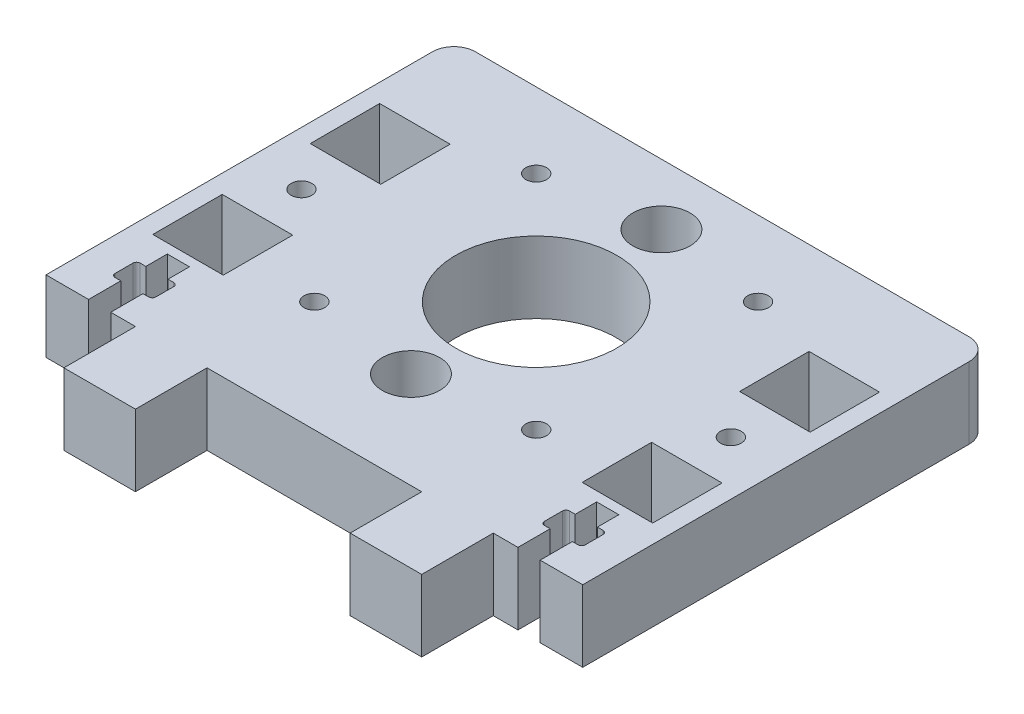
SolidWorks part; units mm, degrees
ref_plane "Front Plane" through (0, 0, 0) normal (0, 0, 1) x (1, 0, 0)
ref_plane "Top Plane" through (0, 0, 0) normal (0, 1, 0) x (1, 0, 0)
ref_plane "Right Plane" through (0, 0, 0) normal (1, 0, 0) x (0, 0, -1)
sketch "Sketch1" plane through (0, 0, 0) normal (0, 1, 0) x (1, 0, 0)
  line L0 (0, 31) -> (0, -8.5) construction
  line L1 (-34.5, 31) -> (0, 31)
  line L2 (-37.5, 28) -> (-37.5, -26)
  line L3 (-37.5, -26) -> (-25, -26)
  line L4 (0, 31) -> (0, 16.25)
  line L5 (0, -6.25) -> (0, -8.5)
  line L6 (0, -16.5) -> (0, -26) construction
  line L7 (-11.25, 5) -> (0, 5) construction
  line L8 (0, -16.5) -> (0, -26)
  line L9 (-30, 18.05) -> (-30, 8.35) construction
  line L10 (-37.5, 2.2) -> (0, 2.2) construction
  line L11 (-34.925, 18.05) -> (-25.075, 18.05)
  line L12 (-34.925, 18.05) -> (-34.925, 8.35)
  line L13 (-34.925, 8.35) -> (-25.075, 8.35)
  line L14 (-25.075, 18.05) -> (-25.075, 8.35)
  line L15 (-34.925, 18.05) -> (-25.075, 8.35) construction
  line L16 (-34.925, 8.35) -> (-25.075, 18.05) construction
  line L17 (-34.925, -3.95) -> (-25.075, -13.65) construction
  line L18 (-34.925, -13.65) -> (-25.075, -3.95) construction
  line L19 (-25.075, -13.65) -> (-25.075, -3.95)
  line L20 (-34.925, -3.95) -> (-25.075, -3.95)
  line L21 (-34.925, -13.65) -> (-34.925, -3.95)
  line L22 (-34.925, -13.65) -> (-25.075, -13.65)
  line L23 (-30, -3.95) -> (-30, -13.65) construction
  line L24 (-30, -8.8) -> (-30, 13.2) construction
  line L25 (0, 5) -> (-15.5, 20.5) construction
  line L35 (-15, -26) -> (0, -26)
  line L43 (-20, -36) -> (-20, -24.65) construction
  line L44 (-15, -26) -> (-15, -36)
  line L45 (-15, -36) -> (-25, -36)
  line L46 (-25, -36) -> (-25, -26)
  arc A1 (-34.5, 31) -> (-37.5, 28) centre (-34.5, 28) ccw
  arc A2 (0, 16.25) -> (0, -6.25) centre (0, 5) ccw
  circle A4 centre (-15.5, 20.5) radius 1.45
  circle A6 centre (-15.5, -10.5) radius 1.45
  circle A7 centre (-30, 2.2) radius 1.45
  arc A10 (0, -8.5) -> (0, -16.5) centre (0, -12.5) ccw
  point P0 (0, 0)
  point P28 (-30, 13.2)
  point P39 (-30, -8.8)
  dimension "D7" = 22.5
  dimension "D17" = 8
  dimension "D14" = 2.9
  dimension "D6" = 3
  dimension "D19" = 2.9
  dimension "D1" = 57
  dimension "D9" = 9.85
  dimension "D10" = 9.7
  dimension "D22" = 10
  dimension "D23" = 10
  dimension "D16" = 17.5
  dimension "D11" = 22
  dimension "D13" = 2.2
  dimension "D3" = 37.5
  dimension "D4" = 31
  dimension "D5" = 15.5
  dimension "D15" = 26
  dimension "D18" = 37.5
  dimension "D20" = 20
  dimension "D8" = 13.5
  dimension "D12" = 30
extrude "MainLayout" add sketch "Sketch1" along normal blind 10
sketch "Sketch2" plane through (0, 10, 0) normal (0, 1, 0) x (1, 0, 0)
  line L0 (-30, -26) -> (-30, -15) construction
  line L1 (-28.45, -21.5) -> (-28.45, -26)
  line L2 (-37.5, -26) -> (-25, -26) construction
  line L3 (-28.45, -15) -> (-31.55, -15)
  line L4 (-31.55, -15) -> (-31.55, -18)
  line L5 (-31.55, -18) -> (-32.35, -18)
  line L6 (-32.85, -18.5) -> (-32.85, -21)
  line L7 (-32.35, -21.5) -> (-31.55, -21.5)
  line L8 (-31.55, -21.5) -> (-31.55, -26)
  line L9 (-31.55, -26) -> (-28.45, -26)
  line L10 (-27.65, -21.5) -> (-28.45, -21.5)
  line L11 (-27.15, -18.5) -> (-27.15, -21)
  line L12 (-28.45, -18) -> (-27.65, -18)
  line L13 (-28.45, -15) -> (-28.45, -18)
  line L14 (0, -26) -> (0, -16.5) construction
  line L30 (-30, -26) -> (-30, -15) construction
  arc A0 (-27.15, -18.5) -> (-27.65, -18) centre (-27.65, -18.5) ccw
  arc A1 (-32.35, -18) -> (-32.85, -18.5) centre (-32.35, -18.5) ccw
  arc A2 (-27.65, -21.5) -> (-27.15, -21) centre (-27.65, -21) ccw
  arc A3 (-32.85, -21) -> (-32.35, -21.5) centre (-32.35, -21) ccw
  point P17 (0, -21.25)
  point P38 (-27.15, -18)
  point P41 (-32.85, -18)
  point P44 (-27.15, -21.5)
  point P47 (-32.85, -21.5)
  dimension "D8" = 0.5
  dimension "D1" = 1.55
  dimension "D2" = 0
  dimension "D3" = 3.5
  dimension "D5" = 11
  dimension "D6" = 2.85
  dimension "D4" = 8
  dimension "D7" = 30
extrude "TSlot" cut sketch "Sketch2" against normal through all
mirror "Mirror1" about plane through (0, 0, 0) normal (1, 0, 0) of "TSlot", "MainLayout"
sketch "Sketch3" plane through (0, 10, 0) normal (0, 1, 0) x (1, 0, 0)
  line L0 (0, 31) -> (0, 0) construction
  line L1 (34.5, 31) -> (-34.5, 31) construction
  line L2 (-11.25, 5) -> (11.25, 5) construction
  circle A0 centre (0, 22.5) radius 4
  circle A1 centre (0, -12.5) radius 4 construction
  circle A2 centre (0, 5) radius 11.25 construction
  dimension "D1" = 17.5
extrude "Cut-Extrude1" cut sketch "Sketch3" against normal through all
equation "\"Y-ROD-SPACING\"=75"
equation "\"Y-BED-OFFSET\"=2"
equation "\"Y-BED-ROD-INSET\"=3.5"
equation "\"T-SLOT-NUT-FILLET-RADIUS\"=0.5"
equation "\"T-SLOT-SCREW-SHAFT-RADIUS\"=1.55"
equation "\"T-SLOT-SCREW-SHAFT-CUTOUT-LENGTH\"=11"
equation "\"T-SLOT-NUT-DEPTH\"=3.5"
equation "\"T-SLOT-NUT-WIDTH\"=2.85"
equation "\"T-SLOT-NUT-END-DISTANCE\"=8"
equation "\"ACRYLIC-TAB-CUTOUT-SIZE\"=\"ACRYLIC-THICKNESS\"+\"ACRYLIC-TAB-TOLERANCE\"*2"
equation "\"ACRYLIC-TAB-WIDTH\"=\"ACRYLIC-THICKNESS\""
equation "\"ACRYLIC-M3-HOLE\"=2.9"
equation "\"SMOOTHROD-CAP-SCREW-DISTANCE\"=20"
equation "\"FRAME-WIDTH-INNER\"=370"
equation "\"NEMA17-HOLE-SPACING\"=31"
equation "\"NEMA17-CENTRAL-CUTOUT\"=22.5"
equation "\"D7@Sketch1\"=\"NEMA17-CENTRAL-CUTOUT\""
equation "\"D5@Sketch1\"=\"NEMA17-HOLE-SPACING\"/2"
equation "\"D4@Sketch1\"=\"NEMA17-HOLE-SPACING\""
equation "\"D19@Sketch1\"=\"ACRYLIC-M3-HOLE\""
equation "\"D14@Sketch1\"=\"ACRYLIC-M3-HOLE\""
equation "\"D9@Sketch1\"=\"ACRYLIC-THICKNESS\"-\"KERF\"*2"
equation "\"D10@Sketch1\"=\"ACRYLIC-TAB-WIDTH\"-\"KERF\"*4"
equation "\"D23@Sketch1\"=\"ACRYLIC-TAB-WIDTH\""
equation "\"D22@Sketch1\"=\"ACRYLIC-TAB-WIDTH\""
equation "\"D5@Sketch2\"=\"T-SLOT-SCREW-SHAFT-CUTOUT-LENGTH\""
equation "\"D4@Sketch2\"=\"T-SLOT-NUT-END-DISTANCE\""
equation "\"D3@Sketch2\"=\"T-SLOT-NUT-DEPTH\""
equation "\"D1@Sketch2\"=\"T-SLOT-SCREW-SHAFT-RADIUS\""
equation "\"D8@Sketch2\"=\"T-SLOT-NUT-FILLET-RADIUS\""
equation "\"Z-BRACKET-REACH\"=57"
equation "\"D1@Sketch1\"=\"Z-BRACKET-REACH\""
equation "\"Z-ROD-SPACING\"=17.5"
equation "\"ACRYLIC-THICKNESS\"=10"
equation "\"TOP-BRACKET-SPACING\"=40"
equation "\"SMOOTHROD-X-LENGTH\"=350"
equation "\"SMOOTHROD-Y-LENGTH\"=350"
equation "\"SMOOTHROD-Z-LENGTH\"=350"
equation "\"SMOOTHROD-TIGHTENING-HEADROOM\"=.25"
equation "\"LEADSCREW-Z-LENGTH\"=300"
equation "\"D16@Sketch1\"=\"Z-ROD-SPACING\""
equation "\"X-ROD-SPACING\"=45"
equation "\"ACRYLIC-THICKNESS2\"=4.5"
equation "\"SCREW-LENGTH-FRAME\"=\"ACRYLIC-THICKNESS\" + 10"
equation "\"SCREW-HEAD-RADIUS\"=6"
equation "\"PRINTED-X-SMOOTHROD-DIAMETER\"=8.8"
equation "\"PRINTED-X-SMOOTHROD-CUTOUT\"=10"
equation "\"PRINTED-X-BASE-HEIGHT\"=10"
equation "\"PRINTED-LM8UU-CUTOUT-SIZE\"=15.5"
equation "\"PRINTED-LM8UU-CUTOUT-LENGTH\"=24.5"
equation "\"PRINTED-X-IDLER-HEIGHT\"=16"
equation "\"PSU-MOUNTING-WIDTH\"=50"
equation "\"PSU-MOUNTING-HEIGHT\"=150"
equation "\"D1@MainLayout\"=\"ACRYLIC-THICKNESS\""
equation "\"Z-ROD-INSET\"=13.5"
equation "\"Y-BELT-TO-ROD-DISTANCE\"=20"
equation "\"SPOOL-HOLDER-ROD-SPACING\"=150"
equation "\"D8@Sketch1\"=\"Z-ROD-INSET\""
equation "\"Y-BED-SCREW-SPACING\"=209"
equation "\"Y-BED-SCREW-CUTOUT-SLOT-HEIGHT\"=2.5"
equation "\"ACRYLIC-TAB-TOLERANCE\"=-.05"
equation "\"SCREW-LENGTH-MOTOR\"=\"ACRYLIC-THICKNESS\" + 5"
equation "\"SCREW-LENGTH-EXTRUDER\"=28"
equation "\"ACRYLIC-X-CARRIAGE-WIDTH\"=55"
equation "\"ACRYLIC-X-CARRIAGE-HEIGHT\"=75"
equation "\"ACRYLIC-X-CARRIAGE-LM8UU-CUTOUT-WIDTH\"=24.25"
equation "\"ACRYLIC-X-CARRIAGE-SCREW-SPACING-X\"=15"
equation "\"ACRYLIC-X-CARRIAGE-SCREW-SPACING-Y\"=33"
equation "\"ACRYLIC-X-CARRIAGE-CENTER-TAB-SPACING\"=14"
equation "\"ACRYLIC-X-CARRIAGE-EXTRUDER-OFFSET\"=26"
equation "\"ACRYLIC-X-CARRIAGE-EXTRUDER-ANGLE\"=90"
equation "\"ACRYLIC-X-CARRIAGE-EXTRUDER-SHELF-DEPTH\"=\"ACRYLIC-X-CARRIAGE-EXTRUDER-OFFSET\" + 28"
equation "\"ACRYLIC-X-CARRIAGE-EXTRUDER-BRACE-SPACING\"=23"
equation "\"ACRYLIC-X-CARRIAGE-EXTRUDER-BRACE-TAB-OFFSET\"=20"
equation "\"ACRYLIC-X-CARRIAGE-EXTRUDER-BRACE-HEIGHT\"=35"
equation "\"ACRYLIC-X-CARRIAGE-EXTRUDER-BRACE-SCREW-SPACING\"=22"
equation "\"KERF\"=0.075"
equation "\"PRINTED-M3-HOLE\"=3.5"
equation "\"PRINTED-M3-NUT-AF\"=6.25"
equation "\"ACRYLIC-X-CARRIAGE-LM8UU-CUTOUT-HEIGHT\"=11.0"
equation "\"ACRYLIC-X-CARRIAGE-DUAL-WIDTH-MULTIPLIER\"=1.65"
equation "\"ACRYLIC-X-CARRIAGE-DUAL-HOTEND-SPACING\"=42"
equation "\"ACRYLIC-X-CARRIAGE-DUAL-WIDTH\"=75"
equation "\"ACRYLIC-X-CARRIAGE-DUAL-FAN-OFFSET\"=52"
equation "\"ACRYLIC-X-CARRIAGE-DUAL-FAN-HEIGHT\"=20"
equation "\"ACRYLIC-X-CARRIAGE-DUAL-HOTEND-SEPARATION\"=36"
equation "\"ACRYLIC-X-CARRIAGE-DUAL-MOUNT-PLATE-DEPTH\"=75"
equation "\"ACRYLIC-X-CARRIAGE-DUAL-MOUNT-BRACE-WIDTH\"=33"
equation "\"ACRYLIC-X-CARRIAGE-DUAL-MOUNT-SCREW-WIDTH\"=40"
equation "\"BLOWER-FAN-WIDTH\"=15"
equation "\"D1@Sketch3\"=\"Z-ROD-SPACING\""
equation "\"ACRYLIC-THICKNESS-TAB-CUTOUT-WIDTH\"=\"ACRYLIC-THICKNESS\"-\"KERF\"*2"
equation "\"ACRYLIC-THICKNESS-TAB-CUTOUT-HEIGHT\"=\"ACRYLIC-TAB-WIDTH\"-\"KERF\"*4"
equation "\"ACRYLIC-THICKNESS2-TAB-CUTOUT-WIDTH\"=\"ACRYLIC-THICKNESS2\"-\"KERF\"*2"
equation "\"ACRYLIC-THICKNESS2-TAB-CUTOUT-HEIGHT\"=\"ACRYLIC-TAB-WIDTH\"-\"KERF\"*4"
equation "\"ACRYLIC-M4-HOLE\"=3.9"
equation "\"D6@Sketch2\"=\"T-SLOT-NUT-WIDTH\""
